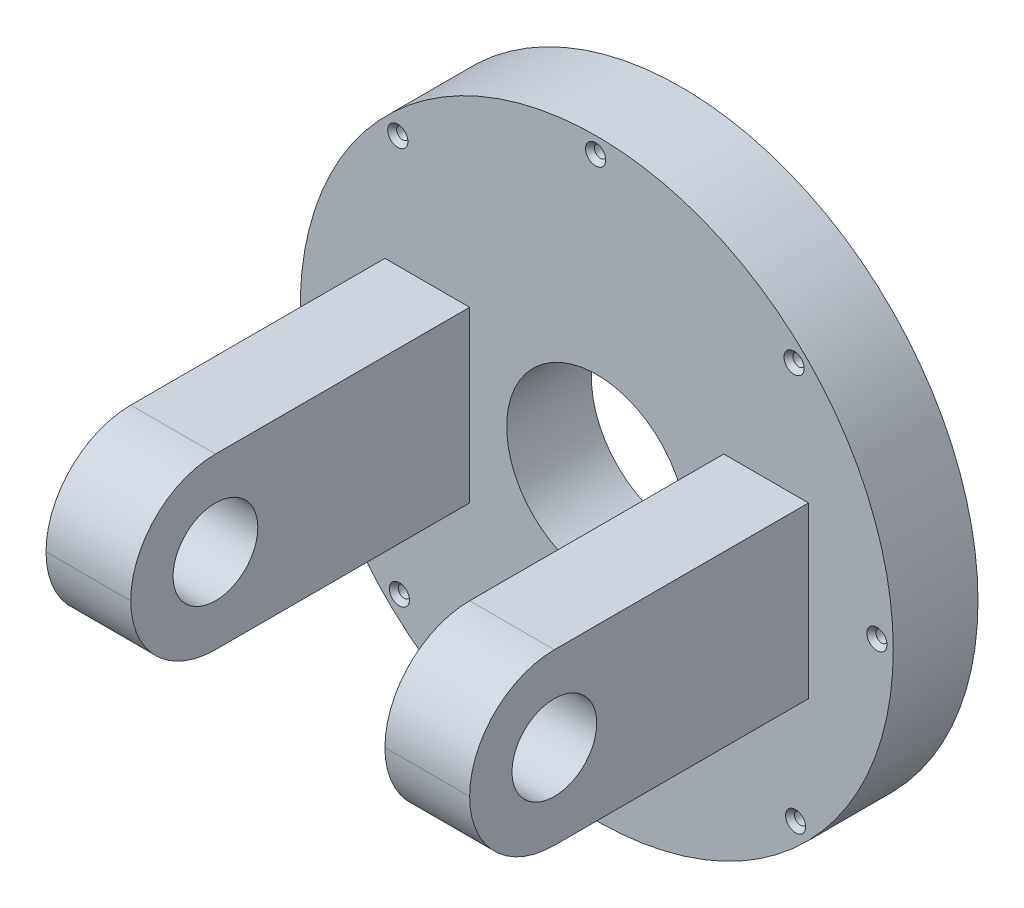
SolidWorks part; units mm, degrees
ref_plane "Front Plane" through (0, 0, 0) normal (0, 0, 1) x (1, 0, 0)
ref_plane "Top Plane" through (0, 0, 0) normal (0, 1, 0) x (1, 0, 0)
ref_plane "Right Plane" through (0, 0, 0) normal (1, 0, 0) x (0, 0, -1)
sketch "Sketch1" plane through (0, 0, 0) normal (0, 0, 1) x (1, 0, 0)
  circle A0 centre (0, 0) radius 44.45
  dimension "D1" = 88.9
extrude "Boss-Extrude1" add sketch "Sketch1" along normal mid plane 12.7
sketch "Sketch2" plane through (0, 0, 6.35) normal (0, 0, 1) x (1, 0, 0)
  circle A0 centre (0, 0) radius 13.5
  dimension "D1" = 27
extrude "Cut-Extrude1" cut sketch "Sketch2" against normal through all
hole_wizard "CSK for #0 Flat Head Machine Screw1" positions "3DSketch2" profile "Sketch4" countersink size "#0" standard "ANSI Inch" end condition through all
sketch3d "3DSketch2"
  circle A0 centre (0, 0, 6.35) radius 44.45 construction
  point P0 (-0.167, 41.9997, 6.35)
  point P5 (0, 0, 50.8)
  dimension "D1" = 42
sketch "Sketch4" plane through (-0.167, 41.9997, 6.35) normal (1, 0, 0) x (0, -1, 0)
  line L0 (0, 0) -> (0, 12.7)
  line L1 (0, 12.7) -> (0.889, 12.7)
  line L2 (0.889, 12.7) -> (0.889, 0.7159)
  line L3 (0.889, 0.7159) -> (1.5113, 0)
  line L5 (1.5113, 0) -> (0, 0)
  line L6 (-0.889, 0.7159) -> (-1.5113, 0) construction
  line L11 (0, -6.35) -> (0, 107.95) construction
  dimension "Thru Hole Dia." = 1.778
  dimension "Thru Hole Depth" = 12.7
  dimension "Near C'Sink Dia." = 3.0226
  dimension "Near C'Sink Angle" = 82
pattern_circular "CirPattern1" count 8 over 360 about axis through (0, 0, 6.35) along (0, 0, -1) of "CSK for #0 Flat Head Machine Screw1"
sketch "Sketch6" plane through (0, 0, 6.35) normal (0, 0, 1) x (1, 0, 0)
  line L0 (0, 0) -> (0, 17.9841) construction
  line L1 (-31.75, 12.7) -> (-19.05, 12.7)
  line L2 (-31.75, 12.7) -> (-31.75, -12.7)
  line L3 (-31.75, -12.7) -> (-19.05, -12.7)
  line L4 (-19.05, 12.7) -> (-19.05, -12.7)
  line L5 (31.75, -12.7) -> (19.05, -12.7)
  line L6 (19.05, 12.7) -> (19.05, -12.7)
  line L7 (31.75, 12.7) -> (19.05, 12.7)
  line L8 (31.75, 12.7) -> (31.75, -12.7)
  circle A0 centre (0, 0) radius 44.45 construction
  point P4 (-19.05, 0)
  dimension "D1" = 12.7
  dimension "D2" = 31.75
  dimension "D3" = 25.4
extrude "Boss-Extrude2" add sketch "Sketch6" along normal blind 50.8
fillet "Fillet1" radius 12.7 4 edges at (-25.4, 12.7, 57.15) (-25.4, -12.7, 57.15) (25.4, -12.7, 57.15) (25.4, 12.7, 57.15)
sketch "Sketch7" plane through (31.75, 0, 0) normal (1, 0, 0) x (0, 0, -1)
  circle A0 centre (-44.45, 0) radius 6.35
  dimension "D1" = 12.7
extrude "Cut-Extrude2" cut sketch "Sketch7" against normal through all
